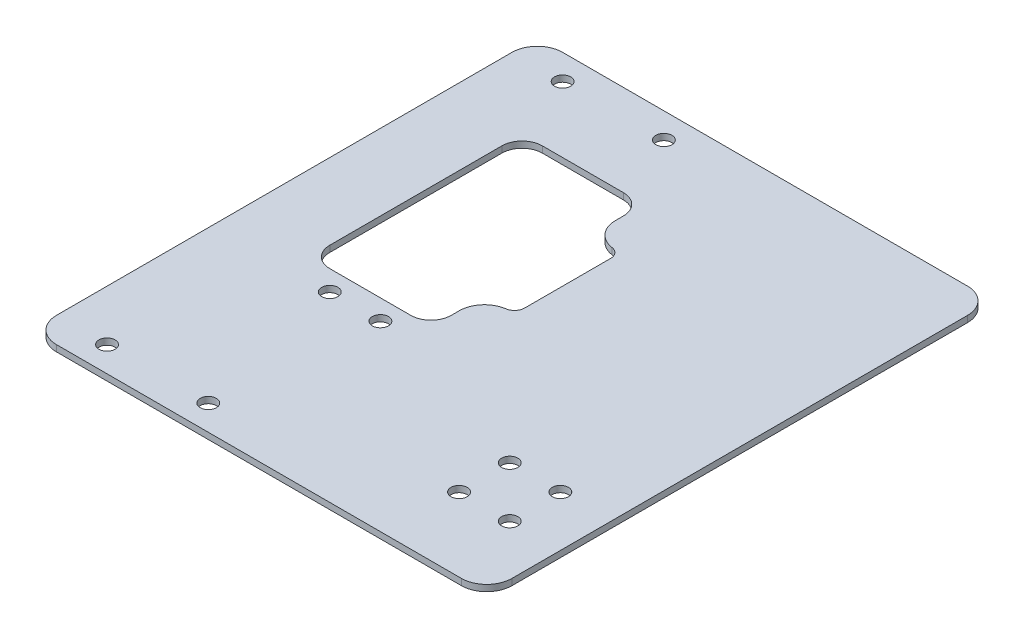
SolidWorks part; units mm, degrees
ref_plane "Front Plane" through (0, 0, 0) normal (0, 0, 1) x (1, 0, 0)
ref_plane "Top Plane" through (0, 0, 0) normal (0, 1, 0) x (1, 0, 0)
ref_plane "Right Plane" through (0, 0, 0) normal (1, 0, 0) x (0, 0, -1)
sketch "Sketch1" plane through (0, 0, 0) normal (0, 1, 0) x (1, 0, 0)
  line L0 (128.27, 0) -> (-128.27, 0) construction
  line L1 (184.15, 63.5) -> (-184.15, 63.5)
  line L2 (184.15, 63.5) -> (184.15, -63.5)
  line L3 (184.15, -63.5) -> (-184.15, -63.5)
  line L4 (-184.15, 63.5) -> (-184.15, -63.5)
  line L5 (184.15, 63.5) -> (-184.15, -63.5) construction
  line L6 (184.15, -63.5) -> (-184.15, 63.5) construction
  line L7 (-128.27, 0) -> (-128.27, 31.75) construction
  line L8 (-128.27, 31.75) -> (-134.62, 31.75) construction
  line L9 (-128.27, 6.35) -> (-134.62, 6.35) construction
  line L12 (-165.1, -12.7) -> (-165.1, 40.64)
  line L15 (-134.62, -12.7) -> (-165.1, -12.7)
  line L17 (-134.62, 40.64) -> (-165.1, 40.64)
  line L18 (0, 63.5) -> (0, -63.5) construction
  line L19 (-134.62, 40.64) -> (-134.62, -12.7)
  line L21 (-95.25, -45.0215) -> (-95.25, -32.3215) construction
  line L22 (-82.55, -45.0215) -> (-95.25, -45.0215) construction
  line L25 (128.27, 31.75) -> (128.27, 6.35) construction
  line L26 (-95.25, -32.3215) -> (-82.55, -32.3215) construction
  line L30 (-82.55, -32.3215) -> (-82.55, -45.0215) construction
  line L31 (184.15, -17.78) -> (154.94, -17.78) construction
  line L32 (146.05, 57.15) -> (184.15, 57.15) construction
  line L33 (154.94, -17.78) -> (142.24, -17.78) construction
  line L34 (146.05, -57.15) -> (184.15, -57.15) construction
  line L35 (-146.05, -57.15) -> (-184.15, -57.15) construction
  line L36 (-146.05, 57.15) -> (-184.15, 57.15) construction
  line L37 (-128.27, 0) -> (-128.27, 6.35) construction
  line L38 (-184.15, -17.78) -> (-154.94, -17.78) construction
  line L39 (-154.94, -17.78) -> (-142.24, -17.78) construction
  line L40 (-134.62, 27.305) -> (-127, 27.305)
  line L41 (-127, 27.305) -> (-127, 0.635)
  line L42 (-127, 0.635) -> (-134.62, 0.635)
  circle A4 centre (171.45, 31.75) radius 2.032 construction
  circle A5 centre (128.27, 31.75) radius 2.032 construction
  circle A6 centre (128.27, 6.35) radius 2.032 construction
  circle A7 centre (171.45, -3.81) radius 2.032 construction
  circle A8 centre (171.45, -57.15) radius 2.032
  circle A9 centre (146.05, -57.15) radius 2.032
  circle A10 centre (171.45, 57.15) radius 2.032
  circle A11 centre (146.05, 57.15) radius 2.032
  circle A12 centre (-146.05, -57.15) radius 2.032
  circle A13 centre (-171.45, -57.15) radius 2.032
  circle A14 centre (-146.05, 57.15) radius 2.032
  circle A15 centre (-171.45, 57.15) radius 2.032
  circle A16 centre (142.24, -17.78) radius 2.032 construction
  circle A17 centre (154.94, -17.78) radius 2.032 construction
  circle A18 centre (-154.94, -17.78) radius 2.032
  circle A19 centre (-142.24, -17.78) radius 2.032
  circle A20 centre (-95.25, -45.0215) radius 2.032
  circle A21 centre (-82.55, -45.0215) radius 2.032
  circle A22 centre (-95.25, -32.3215) radius 2.032
  circle A23 centre (-82.55, -32.3215) radius 2.032
  point P0 (0, 0)
  point P11 (-128.27, 0)
  point P13 (-134.62, 31.75)
  point P17 (-134.62, 6.35)
  point P37 (0, 0)
  point P50 (171.45, 57.15)
  point P51 (146.05, 57.15)
  point P56 (171.45, -57.15)
  point P57 (146.05, -57.15)
  point P84 (-130.81, 27.305)
  point P87 (130.81, 27.305)
  dimension "D5" = 13.335
  dimension "D18" = 4.064
  dimension "D1" = 368.3
  dimension "D2" = 127
  dimension "D3" = 128.27
  dimension "D4" = 25.4
  dimension "D7" = 6.35
  dimension "D8" = 30.48
  dimension "D9" = 53.34
  dimension "D10" = 8.89
  dimension "D11" = 19.05
  dimension "D14" = 12.7
  dimension "D15" = 38.1
  dimension "D16" = 12.7
  dimension "D17" = 38.1
  dimension "D19" = 31.75
  dimension "D20" = 6.35
  dimension "D21" = 6.35
  dimension "D22" = 5.08
  dimension "D23" = 29.21
  dimension "D24" = 12.7
  dimension "D25" = 88.9
  dimension "D26" = 12.7
  dimension "D27" = 7.62
  dimension "D28" = 26.67
  dimension "D29" = 13.335
  dimension "D30" = 18.4785
  dimension "D31" = 12.7
extrude "Boss-Extrude1" add sketch "Sketch1" along normal blind 1.5875 contours L1 L4 L3 L2 A18 A17 A16 A14 A12 A11 A10 A9 A8 L41 L42 L19 L15 L12 L17 L40 A13 A15 A19 region at (6.2259, 0, 0.5157)
sketch "Sketch2" plane through (0, 1.5875, 0) normal (0, 1, 0) x (1, 0, 0)
  line L0 (-69.85, 63.5) -> (-69.85, -63.5)
  line L1 (184.15, 63.5) -> (-184.15, 63.5) construction
  line L2 (184.15, -63.5) -> (-184.15, -63.5) construction
  circle A0 centre (-82.55, -45.0215) radius 2.032 construction
  circle M9 centre (146.05, 57.15) radius 2.032
  circle M10 centre (171.45, 57.15) radius 2.032
  circle M11 centre (146.05, -57.15) radius 2.032
  circle M12 centre (171.45, -57.15) radius 2.032
  line M13 (184.15, 63.5) -> (-184.15, 63.5)
  line M15 (-184.15, -63.5) -> (184.15, -63.5)
  line M16 (184.15, -63.5) -> (184.15, 63.5)
  dimension "D1" = 12.7
extrude "Cut-Extrude1" cut sketch "Sketch2" against normal through all contours L0 M13 M15 M16 M10 M12 M11 M9 region at (56.9863, 1.5875, 0)
fillet "Fillet1" radius 5.08 4 edges at (-134.62, 0.7937, 12.7) (-165.1, 0.7937, 12.7) (-165.1, 0.7937, -40.64) (-134.62, 0.7937, -40.64)
fillet "Fillet3" [suppressed] radius 6.35
fillet "Fillet4" radius 2.54 2 edges at (-127, 0.7937, -0.635) (-127, 0.7937, -27.305)
fillet "Fillet5" radius 6.35 2 edges at (-134.62, 0.7937, -0.635) (-134.62, 0.7937, -27.305)
fillet "Fillet6" radius 6.35 4 edges at (-184.15, 0.7937, -63.5) (-184.15, 0.7937, 63.5) (-69.85, 0.7937, -63.5) (-69.85, 0.7937, 63.5)
equation "\".80.55in\"=0.55"
